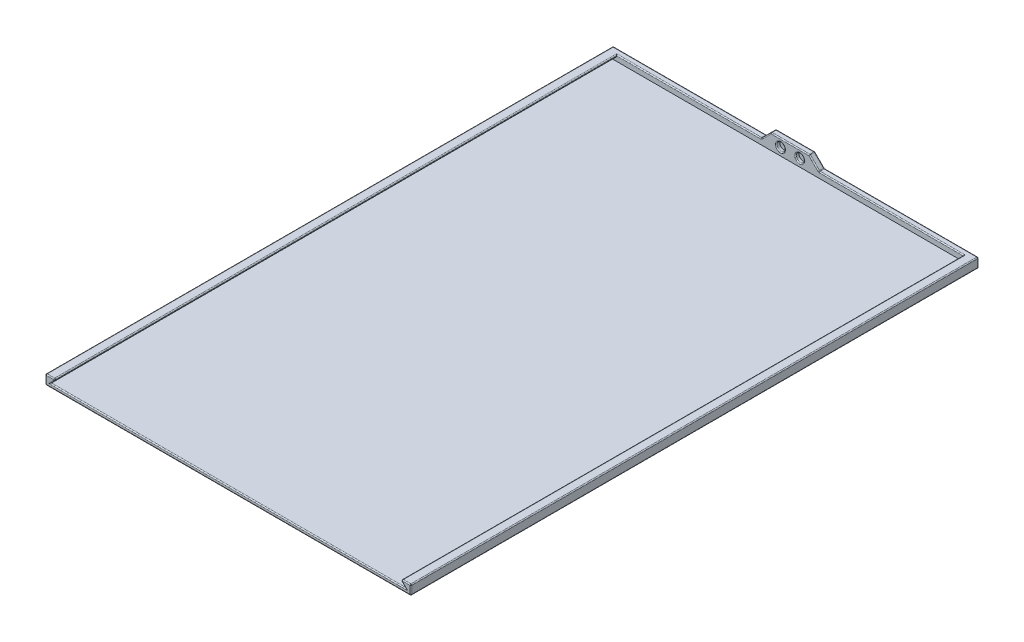
SolidWorks part; units mm, degrees
ref_plane "Front Plane" through (0, 0, 0) normal (0, 0, 1) x (1, 0, 0)
ref_plane "Top Plane" through (0, 0, 0) normal (0, 1, 0) x (1, 0, 0)
ref_plane "Right Plane" through (0, 0, 0) normal (1, 0, 0) x (0, 0, -1)
sketch "Sketch1" plane through (0, 0, 0) normal (0, 0, 1) x (1, 0, 0)
  line L1 (0, 3) -> (4.8, 3)
  line L4 (3, 0) -> (95, 0)
  line L5 (95, -2) -> (0, -2)
  line L7 (95, -2) -> (95, 0)
  line L8 (0, -2) -> (0, 3)
  line L9 (5, 3) -> (5, 2) construction
  line L10 (5, 2) -> (3, 0) construction
  line L11 (3, 0) -> (0, 0) construction
  line L12 (5, 2) -> (5, 0) construction
  line L13 (4.8, 3) -> (4.8, 2.0828)
  line L14 (4.8, 2.0828) -> (2.8586, 0.1414)
  line L15 (2.8586, 0.1414) -> (2.7172, 0)
  line L16 (2.7172, 0) -> (3, 0)
  line L17 (4.8, 3) -> (5, 3) construction
  line L18 (4.8, 3) -> (80, 3)
  line L19 (95, 3) -> (95, 0)
  line L20 (80, 3) -> (85, 8)
  line L21 (85, 8) -> (95, 8)
  line L22 (95, 8) -> (95, 3)
  line L23 (80, 3) -> (95, 3) construction
  line L24 (90, 8) -> (90, 0) construction
  circle A1 centre (90, 4) radius 2.15
  dimension "D11" = 4.3
  dimension "D1" = 2
  dimension "D2" = 5
  dimension "D3" = 3
  dimension "D4" = 5
  dimension "D5" = 1
  dimension "D6" = 2
  dimension "D8" = 95
  dimension "D9" = 5
  dimension "D10" = 10
  dimension "D7" = 0.2
extrude "Boss-Extrude1" add sketch "Sketch1" along normal blind 292.15 contours L16 L15 L14 L13 L1 L8 L5 L7 L4 region at (44.7541, -0.8402, 0)
extrude "Boss-Extrude2" add sketch "Sketch1<3>" against normal blind 3 contours L16 L15 L14 L13 L1 L8 L5 L7 L4 | A1 | L22 L21 L20 L18 L13 L14 L15 L16 L4 L19 A1 region at (44.7541, -0.8402, 0) region at (55.3287, 2.1283, 0) region at (90, 4, 0)
sketch "Sketch1<3>" plane through (0, 0, 0) normal (0, 0, 1) x (1, 0, 0) same geometry as "Sketch1"
extrude "Cut-Extrude1" cut sketch "Sketch1<5>" against normal blind 1.8 contours A1 region at (90, 4, 0)
sketch "Sketch1<5>" plane through (0, 0, 0) normal (0, 0, 1) x (1, 0, 0) same geometry as "Sketch1"
mirror "Mirror1" about plane through (95, 0, 292.15) normal (-1, 0, 0) of bodies 107 104
fillet "Fillet1" radius 0.5 37 edges at (186.2414, 1.0414, 292.15) (185.2, 2.5414, 292.15) (187.6, 3, 292.15) (190, 0.5, 292.15) (95, -2, 292.15) (0, 0.5, 292.15) (2.4, 3, 292.15) (4.8, 2.5414, 292.15) (3.7586, 1.0414, 292.15) (95, 0, 292.15) (107.5, 5.5, 0) (82.5, 5.5, 0) (190, -2, 144.575) (0, -2, 144.575) (82.5, 5.5, -3) (0, 0.5, -3) (95, -2, -3) (190, 0.5, -3) (107.5, 5.5, -3) (85, 8, -1.5) (95, 8, -3) (105, 8, -1.5) (95, 8, 0) (147.6, 3, 0) (110, 3, -1.5) (150, 3, -3) (190, 3, 144.575) (185.2, 3, 146.075) (0, 3, 144.575) (40, 3, -3) (80, 3, -1.5) (42.4, 3, 0) (4.8, 3, 146.075) (4.8, 2.0828, 146.075) (185.2, 2.0828, 146.075) (92.15, 4, 0) (97.85, 4, 0)
